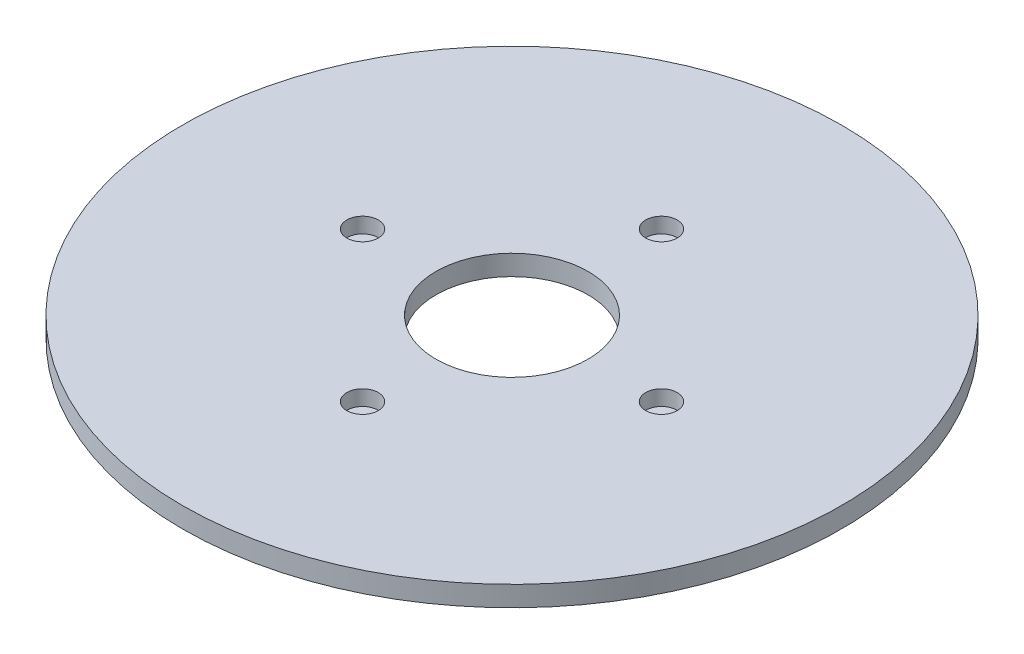
SolidWorks part; units mm, degrees
ref_plane "Front Plane" through (0, 0, 0) normal (0, 0, 1) x (1, 0, 0)
ref_plane "Top Plane" through (0, 0, 0) normal (0, 1, 0) x (1, 0, 0)
ref_plane "Right Plane" through (0, 0, 0) normal (1, 0, 0) x (0, 0, -1)
sketch "Sketch1" plane through (0, 0, 0) normal (0, 1, 0) x (1, 0, 0)
  circle A0 centre (0, 0) radius 65
  dimension "FLANGE_OD" = 130
extrude "Boss-Extrude1" add sketch "Sketch1" along normal blind 4
sketch "Sketch2" plane through (0, 0, 0) normal (0, 1, 0) x (1, 0, 0)
  circle A0 centre (0, 0) radius 15
  dimension "BORE_D" = 30
extrude "Cut-Extrude1" cut sketch "Sketch2" along normal through all
sketch "Sketch3" plane through (0, 4, 0) normal (0, 1, 0) x (1, 0, 0)
  circle A0 centre (0, 0) radius 29.4773 construction
  circle A1 centre (-29.4773, 0) radius 3.0996
  dimension "BOLT_D" = 6.1992
  dimension "BOLT_PCD" = 58.9545
extrude "Cut-Extrude2" cut sketch "Sketch3" against normal blind 3.0306
pattern_circular "CirPattern1" count 4 over 360 about axis through (0, 0, 0) along (0, 1, 0) of "Cut-Extrude2"
